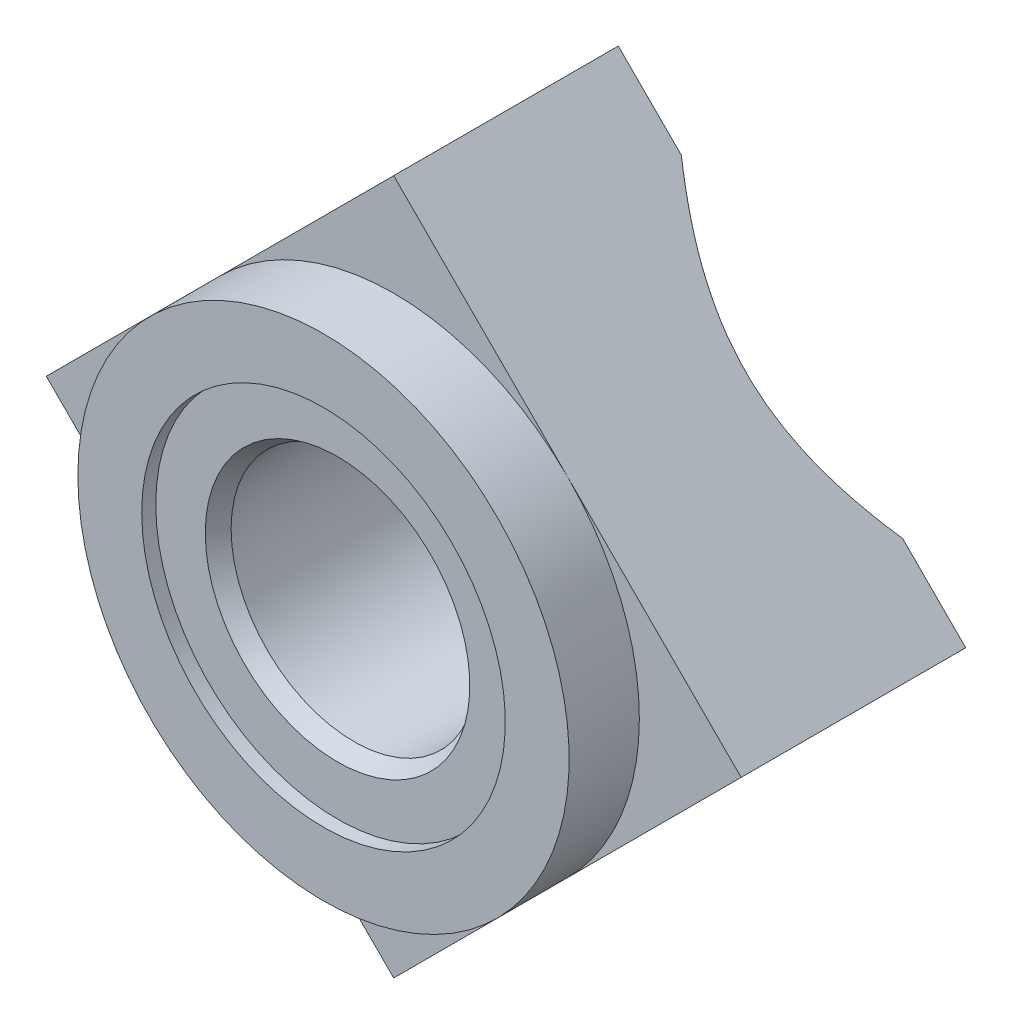
SolidWorks part; units mm, degrees
ref_plane "Front" through (0, 0, 0) normal (0, 0, 1) x (1, 0, 0)
ref_plane "Top" through (0, 0, 0) normal (0, 1, 0) x (1, 0, 0)
ref_plane "Right" through (0, 0, 0) normal (1, 0, 0) x (0, 0, -1)
sketch "Sketch1" plane through (0, 0, 0) normal (0, 0, 1) x (0.7071, 0.7071, 0)
  line L7 (3.5, 3.5) -> (-3.5, 3.5)
  line L8 (-3.5, 3.5) -> (-3.5, -3.5)
  line L9 (-3.5, -3.5) -> (3.5, -3.5)
  line L10 (3.5, -3.5) -> (3.5, 3.5)
  circle A1 centre (0, 0) radius 3.5 construction
  dimension "s" = 7
extrude "BaseNut" add sketch "Sketch1" against normal blind 3.5
sketch "Sketch3" plane through (0, 5.996, -1.0463) normal (-1, 0, 0) x (0, 0, 1)
  line L0 (0.0463, -9.496) -> (0.0463, -10.9458)
  line L2 (0.0463, -9.496) -> (1.0463, -9.496)
  line L3 (-2.4537, -10.9458) -> (1.0463, -10.9458) construction
  line L4 (0, -5.996) -> (7.0423, -5.996) construction
  line L5 (0.0463, -10.9458) -> (1.8463, -10.9458)
  line L6 (1.8463, -10.9458) -> (1.8463, -5.996)
  line L7 (0.8463, -5.996) -> (1.8463, -5.996)
  line L8 (0.8463, -8.586) -> (0.8463, -5.996)
  line L9 (0.8463, -8.586) -> (1.0463, -8.586)
  line L10 (1.0463, -8.586) -> (1.0463, -9.496)
  line L12 (1.0463, -10.9458) -> (1.0463, -5.996) construction
  dimension "D2" = 1
  dimension "D1" = 1
  dimension "s" = 7
revolve "Bearing-Face" cut sketch "Sketch3" angle 360 about L4
sketch "Sketch4" plane through (0.0573, -0.562, -3.5) normal (0, 0, -1) x (-1, 0, 0)
  circle A0 centre (0.0573, 0.562) radius 1.75
  dimension "D1" = 3.5
extrude "Hole" cut sketch "Sketch4" against normal through all
cosmetic thread "ThreadCosmetic1" [suppressed] parameters "D2"=4
chamfer "EndChamfer" distance 0.2333 angle 30 2 edges at (-1.75, 0, -3.5) (-1.75, 0, -0.2) first distance on face at (-1.75, 0, -3.5)
sketch "Sketch8" plane through (0, 0, -3.5) normal (0, 0, -1) x (-1, 0, 0)
  line L0 (-4.9497, 0) -> (0, 4.9497) construction
  line L1 (0, 4.9497) -> (4.9497, 0) construction
  line L2 (4.9497, 0) -> (0, -4.9497) construction
  line L3 (0, -4.9497) -> (-4.9497, 0) construction
  line L4 (-4.9497, 0) -> (0, 4.9497)
  line L5 (0, 4.9497) -> (4.9497, 0)
  line L6 (4.9497, 0) -> (0, -4.9497)
  line L7 (0, -4.9497) -> (-4.9497, 0)
extrude "Extrude1" add sketch "Sketch8" along normal blind 0.7
sketch "Sketch9" plane through (2.5048, 0, 1.645) normal (0, 1, 0) x (0, 0, 1)
  line L0 (-5.145, -2.5048) -> (-5.145, -5.9545)
  line L1 (-5.145, -5.9545) -> (-5.845, -6.6545)
  line L3 (-5.845, -6.6545) -> (-5.845, -2.5048)
  line L4 (-5.845, -2.5048) -> (-5.145, -2.5048)
  line L5 (4.1758, -2.5048) -> (-9.9981, -2.5048) construction
  line L7 (-5.845, -2.5048) -> (-5.845, -7.4545) construction
  dimension "D1" = 45
  dimension "B" = 0.8
revolve "Cut-Revolve1" cut sketch "Sketch9" angle 360 about L5
sketch "Sketch10" plane through (0, 0, 0) normal (0, 1, 0) x (1, 0, 0)
  line L0 (0, 5.447) -> (0, -1.3172) construction
  line L1 (1.5, 3.4903) -> (1.75, 3.4903)
  line L2 (1.75, 3.4903) -> (1.9665, 3.3653)
  line L3 (1.9665, 3.3653) -> (1.75, 3.2403)
  line L4 (1.75, 3.2403) -> (1.5, 3.2403)
  line L5 (1.5, 3.2403) -> (1.5, 3.4903)
  line L6 (-1.75, 3.3653) -> (1.75, 3.3653) construction
  dimension "D1" = 0.25
  dimension "D2" = 3.5
revolve "Cut-Revolve10" [suppressed] cut sketch "Sketch10" angle 360 about L0
pattern_linear "LPattern10" [suppressed] count 10 spacing 0.3 along (0, 0, 1) of bodies 106
equation "\"s@Sketch3\" = \"s@Sketch1\""
equation "\"D1@EndChamfer\" = \"m@BaseNut\" / 15"
equation "\"D2@Sketch10\" = \"D1@Sketch4\""
equation "\"D1@Sketch10\" = (  \"D2@ThreadCosmetic1\" - \"D1@Sketch4\" )  / 2"
equation "\"D3@LPattern10\" = \"D1@Sketch10\" * 1.2"
equation "\"D1@LPattern10\" = \"m@BaseNut\"  / \"D3@LPattern10\" - 2"
